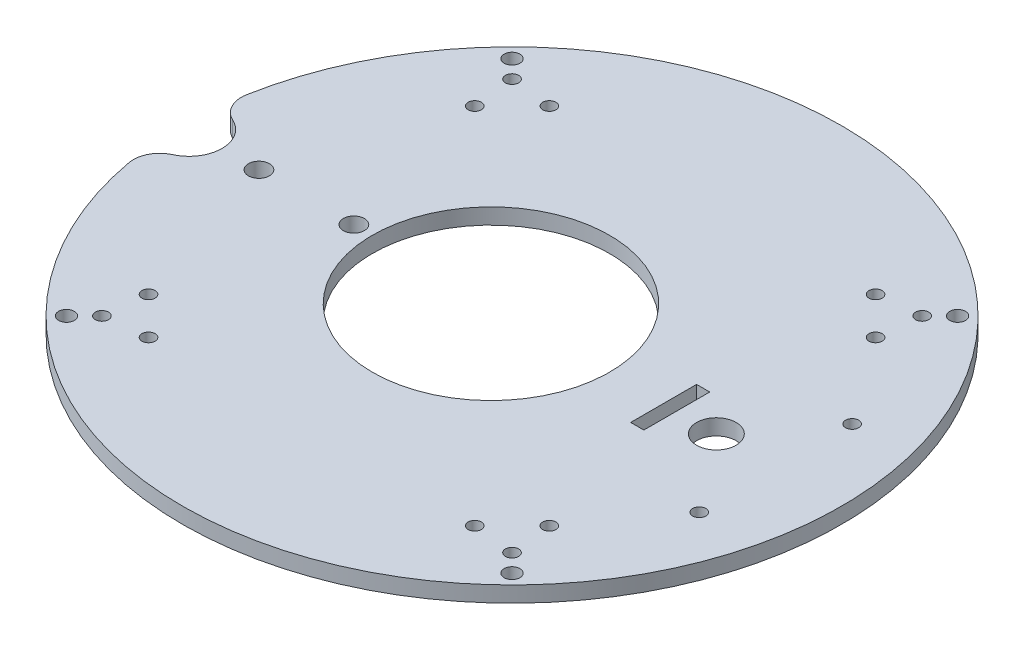
SolidWorks part; units mm, degrees
ref_plane "Front Plane" through (0, 0, 0) normal (0, 0, 1) x (1, 0, 0)
ref_plane "Top Plane" through (0, 0, 0) normal (0, 1, 0) x (1, 0, 0)
ref_plane "Right Plane" through (0, 0, 0) normal (1, 0, 0) x (0, 0, -1)
sketch "Sketch1" plane through (0, 0, 0) normal (0, 1, 0) x (1, 0, 0)
  circle A0 centre (0, 0) radius 125
  circle A1 centre (-96, 0) radius 4
  circle A2 centre (-60, 0) radius 4
  dimension "D1" = 250
  dimension "D2" = 8
  dimension "D3" = 8
  dimension "D4" = 36
  dimension "D5" = 60
extrude "Boss-Extrude1" add sketch "Sketch1" along normal blind 6
sketch "Sketch2" plane through (0, 0, 0) normal (0, 1, 0) x (1, 0, 0)
  circle A0 centre (-77.7817, 77.7817) radius 2.5
  circle A1 centre (77.7817, 77.7817) radius 2.5
  circle A2 centre (77.7817, -77.7817) radius 2.5
  circle A3 centre (-77.7817, -77.7817) radius 2.5
  point P12 (0, 0)
  dimension "D1" = 5
  dimension "D2" = 110
  dimension "D3" = 4
extrude "Bypass Hole for Spring" cut sketch "Sketch2" along normal through all
sketch "Sketch3" plane through (0, 0, 0) normal (0, 1, 0) x (1, 0, 0)
  circle A0 centre (0, 0) radius 37.2703 construction
sketch "Sketch4" plane through (0, 0, 0) normal (0, 1, 0) x (1, 0, 0)
  line L0 (-3.3, 0) -> (3.3, 0) construction
  line L1 (90, 8.9) -> (110, 8.9)
  line L2 (90, 8.9) -> (90, 3.1)
  line L3 (90, 3.1) -> (110, 3.1)
  line L4 (110, 8.9) -> (110, 3.1)
  line L5 (90, 8.9) -> (110, 3.1) construction
  line L6 (90, 3.1) -> (110, 8.9) construction
  line L7 (90, -3.1) -> (110, -8.9) construction
  line L8 (90, -8.9) -> (110, -3.1) construction
  line L9 (110, -8.9) -> (110, -3.1)
  line L10 (90, -3.1) -> (110, -3.1)
  line L11 (90, -8.9) -> (90, -3.1)
  line L12 (90, -8.9) -> (110, -8.9)
  point P0 (100, 6)
  point P13 (100, -6)
  dimension "D1" = 20
  dimension "D2" = 5.8
  dimension "D3" = 3.1
  dimension "D4" = 90
extrude "Platform Pivot" [suppressed] cut sketch "Sketch4" along normal through all
sketch "Sketch5" plane through (0, 0, 0) normal (0, 1, 0) x (1, 0, 0)
  line L8 (0, 0) -> (-8, 0) construction
  circle A7 centre (-8, 0) radius 45
  point P1 (-8.0092, 0)
  dimension "D1" = 8
  dimension "D6" = 90
extrude "Bypass Hole" cut sketch "Sketch5" along normal blind 10
sketch "Sketch7" plane through (0, 0, 0) normal (0, 1, 0) x (1, 0, 0)
  line L1 (-3.3, 0) -> (3.3, 0) construction
  circle A0 centre (100, 29) radius 2.5
  circle A1 centre (100, -29) radius 2.5
  dimension "D1" = 5
  dimension "D2" = 29
  dimension "D3" = 100
extrude "Cut-Extrude3" cut sketch "Sketch7" along normal through all
sketch "Sketch10" plane through (0, 0, 0) normal (0, 1, 0) x (1, 0, 0)
  circle A0 centre (77.5, 0) radius 7.5
  dimension "D1" = 15
  dimension "D2" = 77.5
extrude "Wiring Pass Through" cut sketch "Sketch10" along normal blind 6
sketch "Sketch11" plane through (0, 0, 0) normal (0, 1, 0) x (1, 0, 0)
  line L1 (-135, 12.5) -> (-110, 12.5)
  line L2 (-135, 12.5) -> (-135, -12.5)
  line L3 (-135, -12.5) -> (-110, -12.5)
  line L4 (-110, 12.5) -> (-110, -12.5)
  dimension "D1" = 25
  dimension "D2" = 25
  dimension "D3" = 12.5
  dimension "D4" = 110
extrude "Cut-Extrude7" cut sketch "Sketch11" along normal blind 10
fillet "Fillet2" radius 12.5 2 edges at (-110, 3, 12.5) (-110, 3, -12.5)
fillet "Fillet3" radius 10 2 edges at (-124.3734, 3, 12.5) (-124.3734, 3, -12.5)
sketch "Sketch12" plane through (0, 0, 0) normal (0, 1, 0) x (1, 0, 0)
  line L0 (-3.3, 0) -> (3.3, 0) construction
  line L1 (1.5, 83) -> (-1.5, 83)
  line L2 (1.5, 83) -> (1.5, 93)
  line L3 (1.5, 93) -> (-1.5, 93)
  line L4 (-1.5, 83) -> (-1.5, 93)
  line L5 (-1.5, -83) -> (-1.5, -93)
  line L6 (1.5, -93) -> (-1.5, -93)
  line L7 (1.5, -83) -> (1.5, -93)
  line L8 (1.5, -83) -> (-1.5, -83)
  dimension "D1" = 10
  dimension "D2" = 3
  dimension "D3" = 1.5
  dimension "D4" = 83
extrude "Cut-Extrude8" [suppressed] cut sketch "Sketch12" along normal blind 10
sketch "Sketch13" plane through (0, 0, 0) normal (0, 1, 0) x (1, 0, 0)
  line L0 (61.8718, -76.014) -> (76.014, -61.8718) construction
  line L1 (76.014, -61.8718) -> (84.4993, -84.4993) construction
  line L2 (84.4993, -84.4993) -> (61.8718, -76.014) construction
  line L3 (-76.014, -61.8718) -> (-61.8718, -76.014) construction
  line L4 (-61.8718, -76.014) -> (-84.4993, -84.4993) construction
  line L5 (-84.4993, -84.4993) -> (-76.014, -61.8718) construction
  line L6 (-61.8718, 76.014) -> (-76.014, 61.8718) construction
  line L7 (-76.014, 61.8718) -> (-84.4993, 84.4993) construction
  line L8 (-84.4993, 84.4993) -> (-61.8718, 76.014) construction
  line L9 (76.014, 61.8718) -> (61.8718, 76.014) construction
  line L10 (61.8718, 76.014) -> (84.4993, 84.4993) construction
  line L11 (84.4993, 84.4993) -> (76.014, 61.8718) construction
  circle A0 centre (76.014, -61.8718) radius 2.5
  circle A1 centre (61.8718, -76.014) radius 2.5
  circle A2 centre (84.4993, -84.4993) radius 3
  circle A3 centre (-61.8718, -76.014) radius 2.5
  circle A4 centre (-76.014, -61.8718) radius 2.5
  circle A5 centre (-84.4993, -84.4993) radius 3
  circle A6 centre (-76.014, 61.8718) radius 2.5
  circle A7 centre (-61.8718, 76.014) radius 2.5
  circle A8 centre (-84.4993, 84.4993) radius 3
  circle A9 centre (61.8718, 76.014) radius 2.5
  circle A10 centre (76.014, 61.8718) radius 2.5
  circle A11 centre (84.4993, 84.4993) radius 3
  point P31 (0, 0)
  dimension "D1" = 5
  dimension "D2" = 5
  dimension "D3" = 6
  dimension "D4" = 97.5
  dimension "D5" = 76.014
  dimension "D6" = 4
extrude "Cut-Extrude9" cut sketch "Sketch13" along normal blind 10
sketch "Sketch14" plane through (0, 0, 0) normal (0, 1, 0) x (1, 0, 0)
  line L1 (62.5, 12.5) -> (57.5, 12.5)
  line L2 (62.5, 12.5) -> (62.5, -12.5)
  line L3 (62.5, -12.5) -> (57.5, -12.5)
  line L4 (57.5, 12.5) -> (57.5, -12.5)
  line L5 (62.5, 12.5) -> (57.5, -12.5) construction
  line L6 (62.5, -12.5) -> (57.5, 12.5) construction
  point P0 (60, 0)
  dimension "D1" = 5
  dimension "D2" = 25
  dimension "D3" = 12.5
  dimension "D4" = 60
extrude "Cut-Extrude10" cut sketch "Sketch14" along normal blind 6
